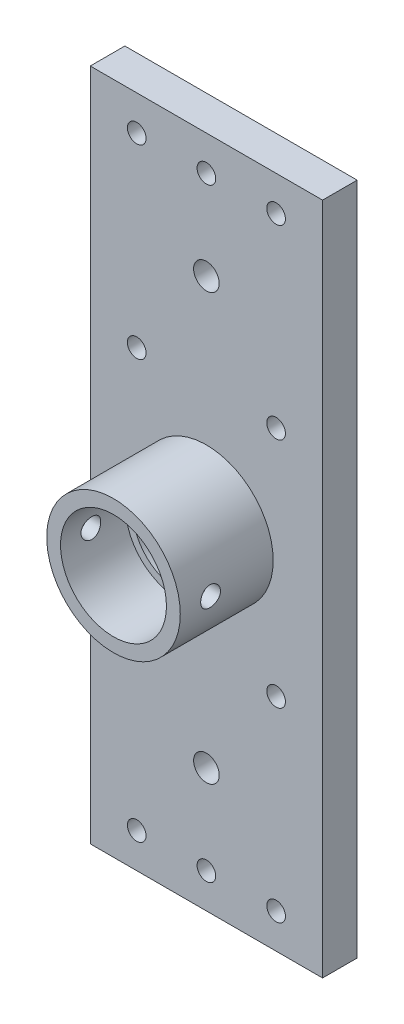
SolidWorks part; units mm, degrees
ref_plane "Front Plane" through (0, 0, 0) normal (0, 0, 1) x (1, 0, 0)
ref_plane "Top Plane" through (0, 0, 0) normal (0, 1, 0) x (1, 0, 0)
ref_plane "Right Plane" through (0, 0, 0) normal (1, 0, 0) x (0, 0, -1)
sketch "Sketch1" plane through (0, 0, 0) normal (0, 0, 1) x (1, 0, 0)
  line L5 (-31.75, 92.075) -> (31.75, 92.075)
  line L6 (-31.75, 92.075) -> (-31.75, -92.075)
  line L7 (-31.75, -92.075) -> (31.75, -92.075)
  line L8 (31.75, 92.075) -> (31.75, -92.075)
  line L9 (-31.75, 92.075) -> (31.75, -92.075) construction
  line L10 (-31.75, -92.075) -> (31.75, 92.075) construction
  point P5 (0, 0)
  dimension "D1" = 63.5
  dimension "D2" = 184.15
extrude "Boss-Extrude1" add sketch "Sketch1" along normal blind 4.7625 and the other way blind 4.699
sketch "Sketch3" plane through (0, 0, 4.7625) normal (0, 0, 1) x (1, 0, 0)
  circle A0 centre (0, 0) radius 6.35
  dimension "D1" = 12.7
extrude "Cut-Extrude1" cut sketch "Sketch3" against normal blind 0.508
sketch "Sketch4" plane through (0, 0, 4.7625) normal (0, 0, 1) x (1, 0, 0)
  circle A0 centre (0, 0) radius 18.2562
  dimension "D1" = 36.5125
extrude "Boss-Extrude2" add sketch "Sketch4" along normal blind 38.1 contours A0
sketch "Sketch5" plane through (0, 0, 42.8625) normal (0, 0, 1) x (1, 0, 0)
  circle A0 centre (0, 0) radius 12.4619
  dimension "D1" = 24.9237
extrude "Cut-Extrude2" cut sketch "Sketch5" against normal blind 38.1 contours A0
sketch "Sketch7" plane through (0, 0, 42.8625) normal (0, 0, 1) x (1, 0, 0)
  circle A0 centre (0, 0) radius 14.2875
  dimension "D1" = 28.575
extrude "Cut-Extrude3" cut sketch "Sketch7" against normal blind 30.48
hole_wizard "#10 Clearance Hole1" positions "Sketch8" profile "Sketch9" hole size "#10" standard "ANSI Inch" end condition up to next
sketch "Sketch8" plane through (0, 0, 4.7625) normal (0, 0, 1) x (1, 0, 0)
  line L0 (31.75, 92.075) -> (-31.75, 92.075) construction
  line L1 (31.75, -92.075) -> (31.75, 92.075) construction
  line L2 (-31.75, 92.075) -> (-31.75, -92.075) construction
  line L3 (-31.75, -92.075) -> (31.75, -92.075) construction
  point P0 (-19.05, 82.55)
  point P2 (-19.05, -82.55)
  point P4 (19.05, -82.55)
  point P6 (19.05, 82.55)
  point P23 (-19.05, 31.75)
  point P26 (-19.05, -31.75)
  point P28 (19.05, -31.75)
  point P30 (19.05, 31.75)
  point P31 (0, 82.55)
  point P33 (0, -82.55)
  dimension "D1" = 9.525
  dimension "D2" = 12.7
  dimension "D3" = 9.525
  dimension "D4" = 12.7
  dimension "D5" = 9.525
  dimension "D6" = 12.7
  dimension "D7" = 12.7
  dimension "D8" = 9.525
  dimension "D11" = 50.8
  dimension "D12" = 50.8
  dimension "D13" = 50.8
  dimension "D14" = 50.8
sketch "Sketch9" plane through (-19.05, 82.55, 4.7625) normal (1, 0, 0) x (0, -1, 0)
  line L0 (0, 0) -> (0, 9.4615)
  line L1 (0, 9.4615) -> (2.5527, 9.4615)
  line L2 (2.5527, 9.4615) -> (2.5527, 0)
  line L5 (2.5527, 0) -> (0, 0)
  line L11 (0, -6.35) -> (0, 107.95) construction
  dimension "Thru Hole Dia." = 5.1054
  dimension "Thru Hole Depth" = 9.4615
sketch "Sketch10" plane through (0, 0, 4.7625) normal (0, 0, 1) x (1, 0, 0)
  line L0 (31.75, 41.275) -> (-31.75, 41.275)
  line L1 (31.75, -92.075) -> (31.75, 92.075) construction
  line L2 (-31.75, 92.075) -> (-31.75, -92.075) construction
  line L3 (31.75, -41.275) -> (-31.75, -41.275)
  point P8 (-31.75, 0)
  dimension "D1" = 41.275
  dimension "D2" = 41.275
sketch "Sketch13" plane through (0, 0, 42.8625) normal (0, 0, 1) x (1, 0, 0)
  circle A0 centre (0, 0) radius 14.478
  dimension "D1" = 28.956
extrude "Cut-Extrude4" cut sketch "Sketch13" against normal up to surface (30.48 mm away) up to face at (14.2875, 0, 12.3825)
sketch "Sketch14" plane through (0, 0, 42.8625) normal (0, 0, 1) x (1, 0, 0)
  circle A0 centre (0, 0) radius 18.2562
extrude "Cut-Extrude5" cut sketch "Sketch14" against normal blind 12.7
sketch "Sketch15" plane through (0, -92.075, 0) normal (0, -1, 0) x (-1, 0, 0)
hole_wizard "#3 (0.213) Diameter Hole1" positions "3DSketch7" profile "Sketch22" hole size "#3" standard "ANSI Inch" end condition through all
sketch3d "3DSketch7"
  point P0 (18.2562, 0, 21.8735)
sketch "Sketch22" plane through (18.2562, 0, 21.8735) normal (0, 1, 0) x (0, 0, -1)
  line L0 (0, 0) -> (0, 50.0063)
  line L1 (0, 50.0063) -> (2.7051, 50.0063)
  line L2 (2.7051, 50.0063) -> (2.7051, 0)
  line L5 (2.7051, 0) -> (0, 0)
  line L11 (0, -6.35) -> (0, 107.95) construction
  dimension "Thru Hole Dia." = 5.4102
  dimension "Thru Hole Depth" = 50.0063
hole_wizard "CBORE for M6 Hex Head Bolt1" positions "Sketch25" profile "Sketch26" counterbore size "M6" standard "ANSI Metric" end condition through all
sketch "Sketch25" plane through (0, 0, -4.699) normal (0, 0, -1) x (-1, 0, 0)
  line L0 (-31.75, 41.275) -> (31.75, 41.275) construction
  line L1 (-31.75, -41.275) -> (31.75, -41.275) construction
  point P0 (0, -58.2083)
  point P2 (0, 58.2083)
  dimension "D1" = 16.9333
  dimension "D2" = 16.9333
sketch "Sketch26" plane through (0, -58.2083, -4.699) normal (1, 0, 0) x (0, 1, 0)
  line L0 (0, 0) -> (0, 34.8615)
  line L1 (0, 34.8615) -> (3.5, 34.8615)
  line L3 (3.5, 34.8615) -> (3.5, 4.38)
  line L4 (3.5, 4.38) -> (7.275, 4.38)
  line L5 (7.275, 4.38) -> (7.275, 0)
  line L7 (7.275, 0) -> (0, 0)
  line L11 (0, -6.35) -> (0, 107.95) construction
  dimension "Thru Hole Dia." = 7
  dimension "Thru Hole Depth" = 34.8615
  dimension "C'Bore Dia." = 14.55
  dimension "C'Bore Depth" = 4.38
sketch "Sketch28" plane through (0, 0, 4.7625) normal (0, 0, 1) x (1, 0, 0)
  text T0 "Bomb Botz v10"
extrude "Boss-Extrude4" add sketch "Sketch28" against normal blind 1.27
